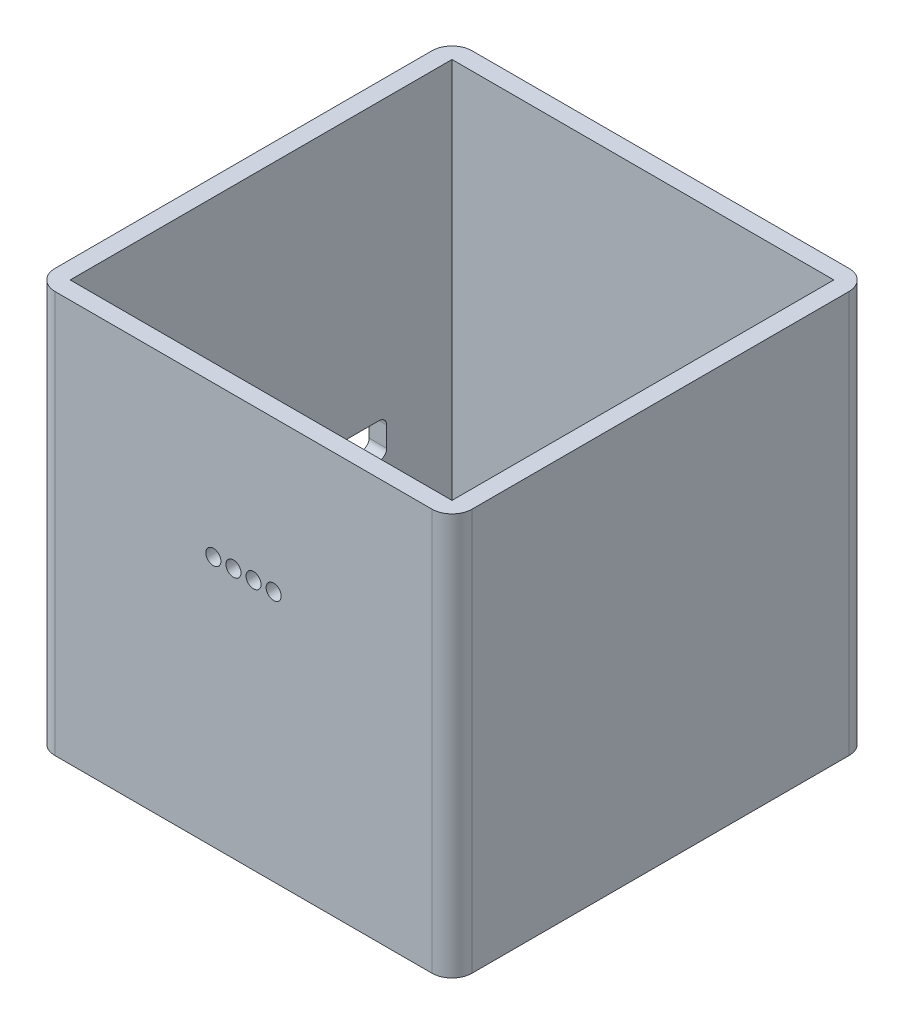
SolidWorks part; units mm, degrees
ref_plane "Front Plane" through (0, 0, 0) normal (0, 0, 1) x (1, 0, 0)
ref_plane "Top Plane" through (0, 0, 0) normal (0, 1, 0) x (1, 0, 0)
ref_plane "Right Plane" through (0, 0, 0) normal (1, 0, 0) x (0, 0, -1)
sketch "Sketch4" plane through (0, 0, 0) normal (0, 1, 0) x (1, 0, 0)
  line L1 (-41.5, 41.5) -> (41.5, 41.5)
  line L2 (-41.5, 41.5) -> (-41.5, -41.5)
  line L3 (-41.5, -41.5) -> (41.5, -41.5)
  line L4 (41.5, 41.5) -> (41.5, -41.5)
extrude "Boss-Extrude2" add sketch "Sketch4" along normal blind 40 and the other way blind 40
sketch "Sketch5" plane through (0, 0, 0) normal (0, 1, 0) x (1, 0, 0)
  line L1 (-38, 38) -> (38, 38)
  line L2 (-38, 38) -> (-38, -38)
  line L3 (-38, -38) -> (38, -38)
  line L4 (38, 38) -> (38, -38)
extrude "Cut-Extrude1" cut sketch "Sketch5" against normal blind 37.5 and the other way blind 50
sketch "Sketch6" plane through (0, 0, 0) normal (0, 0, 1) x (1, 0, 0)
  circle A0 centre (2, 10) radius 1.5
  circle A1 centre (6, 10) radius 1.5
  circle A2 centre (-2, 10) radius 1.5
  circle A3 centre (-6, 10) radius 1.5
extrude "Cut-Extrude2" cut sketch "Sketch6" along normal blind 74.5 and the other way blind 5
sketch "Sketch8" plane through (0, 0, 0) normal (0, 0, 1) x (1, 0, 0)
  line L0 (0, -41.25) -> (0, 41.25) construction
  circle A0 centre (0, -9) radius 1
  circle A1 centre (2.5, -9) radius 1
  circle A2 centre (0, -6.5) radius 1
  circle A3 centre (-2.5, -9) radius 1
  circle A4 centre (0, -11.5) radius 1
extrude "Cut-Extrude3" cut sketch "Sketch8" against normal blind 70.5
sketch "Sketch9" plane through (0, 0, 0) normal (0, 0, 1) x (1, 0, 0)
  line L1 (18, -15) -> (30, -15)
  line L2 (18, -15) -> (18, -22)
  line L3 (18, -22) -> (30, -22)
  line L4 (30, -15) -> (30, -22)
extrude "Cut-Extrude4" cut sketch "Sketch9" against normal blind 108.5
fillet "Fillet2" radius 1 4 edges at (18, -22, -39.75) (30, -22, -39.75) (18, -15, -39.75) (30, -15, -39.75)
fillet "Fillet3" radius 4 4 edges at (-41.5, 0, 41.5) (41.5, 0, -41.5) (41.5, 0, 41.5) (-41.5, 0, -41.5)
sketch "Sketch10" plane through (0, 0, 0) normal (1, 0, 0) x (0, 0, -1)
  line L1 (15, -15) -> (25, -15)
  line L2 (15, -15) -> (15, -22)
  line L3 (15, -22) -> (25, -22)
  line L4 (25, -15) -> (25, -22)
  point P4 (0, 0)
  point P5 (0, 0)
extrude "Cut-Extrude5" cut sketch "Sketch10" against normal blind 83
fillet "Fillet4" radius 1.5 4 edges at (-39.75, -22, -15) (-39.75, -22, -25) (-39.75, -15, -15) (-39.75, -15, -25)
sketch "Sketch11" plane through (0, -37.5, 0) normal (0, 1, 0) x (1, 0, 0)
  circle A0 centre (30.875, 27.5) radius 2
  circle A1 centre (-30.875, 27.5) radius 2
  circle A2 centre (-30.875, -27.5) radius 2
  circle A3 centre (30.875, -27.5) radius 2
  point P6 (0, 0)
  point P9 (0, 0)
extrude "Boss-Extrude4" add sketch "Sketch11" along normal blind 5
sketch "Sketch12" plane through (0, -37.5, 0) normal (0, 1, 0) x (1, 0, 0)
  circle A0 centre (-30.875, 27.5) radius 1.2
  circle A1 centre (30.875, 27.5) radius 1.2
  circle A2 centre (-30.875, -27.5) radius 1.2
  circle A3 centre (30.875, -27.5) radius 1.2
extrude "Boss-Extrude5" add sketch "Sketch12" along normal blind 10
